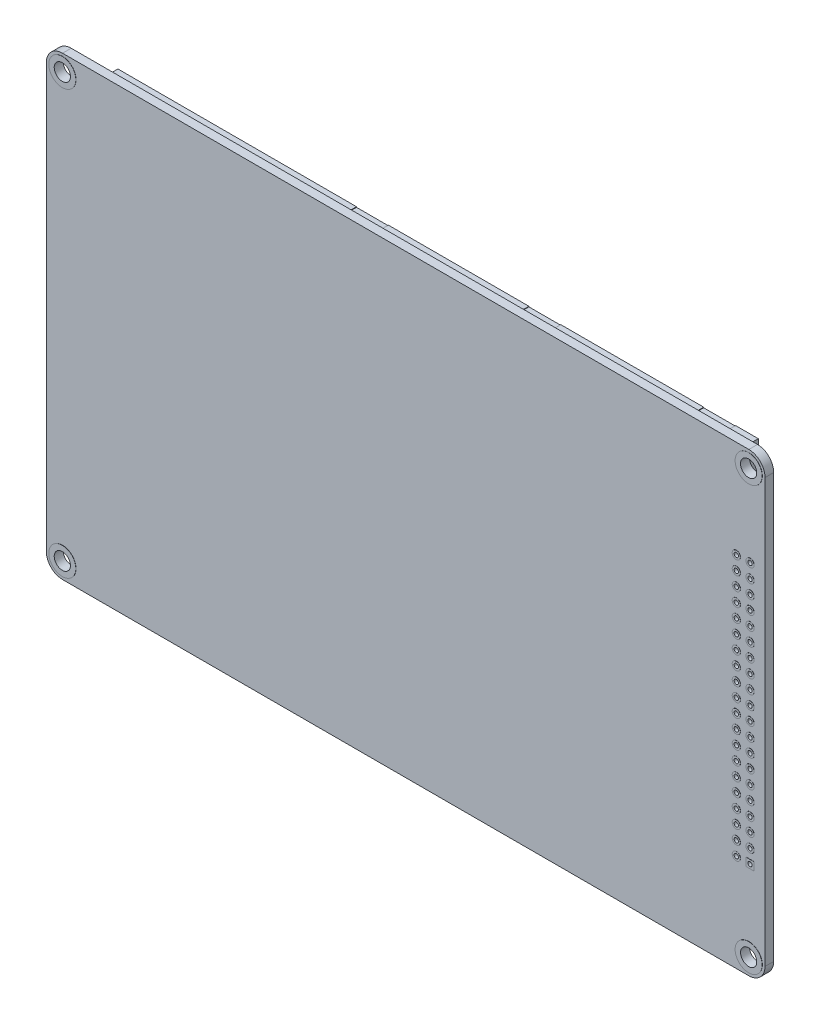
SolidWorks part; units mm, degrees
ref_plane "Plan de face" through (0, 0, 0) normal (0, 0, 1) x (1, 0, 0)
ref_plane "Plan de dessus" through (0, 0, 0) normal (0, 1, 0) x (1, 0, 0)
ref_plane "Plan de droite" through (0, 0, 0) normal (1, 0, 0) x (0, 0, -1)
sketch "Esquisse1" plane through (0, 0, 0) normal (0, 0, 1) x (1, 0, 0)
  line L1 (-66.5, -42.175) -> (66.5, -42.175)
  line L2 (-66.5, -42.175) -> (-66.5, 42.175)
  line L3 (-66.5, 42.175) -> (66.5, 42.175)
  line L4 (66.5, -42.175) -> (66.5, 42.175)
  line L5 (-66.5, -42.175) -> (66.5, 42.175) construction
  line L6 (-66.5, 42.175) -> (66.5, -42.175) construction
  point P0 (0, 0)
  dimension "D1" = 84.35
  dimension "D2" = 133
extrude "Boss.-Extru.1" add sketch "Esquisse1" along normal blind 1.6
sketch "Esquisse2" plane through (0, 0, 1.6) normal (0, 0, 1) x (1, 0, 0)
  line L0 (-66.5, -42.175) -> (66.5, -42.175) construction
  line L1 (-66.5, 42.175) -> (-66.5, -42.175) construction
  line L2 (66.5, -42.175) -> (66.5, 42.175) construction
  line L3 (66.5, 42.175) -> (-66.5, 42.175) construction
  circle A0 centre (-63.5, -39.175) radius 1.5
  circle A1 centre (63.5, -39.175) radius 1.5
  circle A2 centre (-63.5, 39.175) radius 1.5
  circle A3 centre (63.5, 39.175) radius 1.5
  dimension "D1" = 3
  dimension "D6" = 3
  dimension "D7" = 3
  dimension "D2" = 3
  dimension "D3" = 3
  dimension "D4" = 2
  dimension "D5" = 2
extrude "Enlèv. mat.-Extru.1" cut sketch "Esquisse2" against normal blind 10
sketch "Esquisse3" plane through (0, 0, 1.6) normal (0, 0, 1) x (1, 0, 0)
  circle A0 centre (-63.5, -39.175) radius 1.5
  circle A1 centre (-63.5, -39.175) radius 2.5
  circle A2 centre (63.5, -39.175) radius 2.5
  circle A3 centre (63.5, -39.175) radius 1.5
  circle A4 centre (-63.5, 39.175) radius 2.5
  circle A5 centre (-63.5, 39.175) radius 1.5
  circle A6 centre (63.5, 39.175) radius 2.5
  circle A7 centre (63.5, 39.175) radius 1.5
  dimension "D1" = 5
  dimension "D4" = 3
  dimension "D2" = 2
  dimension "D3" = 2
extrude "Boss.-Extru.2" add sketch "Esquisse3" along normal blind 0.035
sketch "Esquisse4" plane through (-66.5, 0, 0) normal (-1, 0, 0) x (0, 0, 1)
  line L0 (1.6, 42.175) -> (0, -42.175) construction
  line L1 (0, -42.175) -> (1.6, -42.175) construction
  line L2 (1.6, -42.175) -> (0, 42.175) construction
  point P4 (0.8, 0)
ref_axis "Axe1" through (-66.5, 0, 0.8) along (-1, 0, 0)
pattern_circular "Répétition circulaire1" count 2 every 180 about axis through (-66.5, 0, 0.8) along (-1, 0, 0) of "Boss.-Extru.2"
sketch "Esquisse5" plane through (0, 0, 1.6) normal (0, 0, 1) x (1, 0, 0)
  line L0 (66.5, -42.175) -> (66.5, 42.175) construction
  line L1 (-66.5, -42.175) -> (66.5, -42.175) construction
  circle A0 centre (63.75, -24.13) radius 0.4
  circle A1 centre (61.21, -24.13) radius 0.4
  circle A2 centre (63.75, -21.59) radius 0.4
  circle A3 centre (61.21, -21.59) radius 0.4
  circle A4 centre (63.75, -19.05) radius 0.4
  circle A5 centre (61.21, -19.05) radius 0.4
  circle A6 centre (63.75, -16.51) radius 0.4
  circle A7 centre (61.21, -16.51) radius 0.4
  circle A8 centre (63.75, -13.97) radius 0.4
  circle A9 centre (61.21, -13.97) radius 0.4
  circle A10 centre (63.75, -11.43) radius 0.4
  circle A11 centre (61.21, -11.43) radius 0.4
  circle A12 centre (63.75, -8.89) radius 0.4
  circle A13 centre (61.21, -8.89) radius 0.4
  circle A14 centre (63.75, -6.35) radius 0.4
  circle A15 centre (61.21, -6.35) radius 0.4
  circle A16 centre (63.75, -3.81) radius 0.4
  circle A17 centre (61.21, -3.81) radius 0.4
  circle A18 centre (63.75, -1.27) radius 0.4
  circle A19 centre (61.21, -1.27) radius 0.4
  circle A20 centre (63.75, 1.27) radius 0.4
  circle A21 centre (61.21, 1.27) radius 0.4
  circle A22 centre (63.75, 3.81) radius 0.4
  circle A23 centre (61.21, 3.81) radius 0.4
  circle A24 centre (63.75, 6.35) radius 0.4
  circle A25 centre (61.21, 6.35) radius 0.4
  circle A26 centre (63.75, 8.89) radius 0.4
  circle A27 centre (61.21, 8.89) radius 0.4
  circle A28 centre (63.75, 11.43) radius 0.4
  circle A29 centre (61.21, 11.43) radius 0.4
  circle A30 centre (63.75, 13.97) radius 0.4
  circle A31 centre (61.21, 13.97) radius 0.4
  circle A32 centre (63.75, 16.51) radius 0.4
  circle A33 centre (61.21, 16.51) radius 0.4
  circle A34 centre (63.75, 19.05) radius 0.4
  circle A35 centre (61.21, 19.05) radius 0.4
  circle A36 centre (63.75, 21.59) radius 0.4
  circle A37 centre (61.21, 21.59) radius 0.4
  circle A38 centre (63.75, 24.13) radius 0.4
  circle A39 centre (61.21, 24.13) radius 0.4
  dimension "D1" = 0.8
  dimension "D6" = 48.26
  dimension "D2" = 2
  dimension "D3" = 20
  dimension "D4" = 2.75
  dimension "D5" = 18.045
extrude "Enlèv. mat.-Extru.2" cut sketch "Esquisse5" against normal through all
sketch "Esquisse6" plane through (0, 0, 1.6) normal (0, 0, 1) x (1, 0, 0)
  line L1 (63, -23.38) -> (64.5, -23.38)
  line L2 (63, -23.38) -> (63, -24.88)
  line L3 (63, -24.88) -> (64.5, -24.88)
  line L4 (64.5, -23.38) -> (64.5, -24.88)
  line L5 (63, -23.38) -> (64.5, -24.88) construction
  line L6 (63, -24.88) -> (64.5, -23.38) construction
  circle A0 centre (63.75, -24.13) radius 0.4
  circle A1 centre (63.75, -24.13) radius 0.4 construction
  circle A2 centre (61.21, -24.13) radius 0.4
  circle A3 centre (61.21, -24.13) radius 0.75
  circle A4 centre (61.21, -21.59) radius 0.75
  circle A5 centre (61.21, -21.59) radius 0.4
  circle A6 centre (61.21, -19.05) radius 0.75
  circle A7 centre (61.21, -19.05) radius 0.4
  circle A8 centre (61.21, -16.51) radius 0.75
  circle A9 centre (61.21, -16.51) radius 0.4
  circle A10 centre (61.21, -13.97) radius 0.75
  circle A11 centre (61.21, -13.97) radius 0.4
  circle A12 centre (61.21, -11.43) radius 0.75
  circle A13 centre (61.21, -11.43) radius 0.4
  circle A14 centre (61.21, -8.89) radius 0.75
  circle A15 centre (61.21, -8.89) radius 0.4
  circle A16 centre (61.21, -6.35) radius 0.75
  circle A17 centre (61.21, -6.35) radius 0.4
  circle A18 centre (61.21, -3.81) radius 0.75
  circle A19 centre (61.21, -3.81) radius 0.4
  circle A20 centre (61.21, -1.27) radius 0.75
  circle A21 centre (61.21, -1.27) radius 0.4
  circle A22 centre (61.21, 1.27) radius 0.75
  circle A23 centre (61.21, 1.27) radius 0.4
  circle A24 centre (61.21, 3.81) radius 0.75
  circle A25 centre (61.21, 3.81) radius 0.4
  circle A26 centre (61.21, 6.35) radius 0.75
  circle A27 centre (61.21, 6.35) radius 0.4
  circle A28 centre (61.21, 8.89) radius 0.75
  circle A29 centre (61.21, 8.89) radius 0.4
  circle A30 centre (61.21, 11.43) radius 0.75
  circle A31 centre (61.21, 11.43) radius 0.4
  circle A32 centre (61.21, 13.97) radius 0.75
  circle A33 centre (61.21, 13.97) radius 0.4
  circle A34 centre (61.21, 16.51) radius 0.75
  circle A35 centre (61.21, 16.51) radius 0.4
  circle A36 centre (61.21, 19.05) radius 0.75
  circle A37 centre (61.21, 19.05) radius 0.4
  circle A38 centre (61.21, 21.59) radius 0.75
  circle A39 centre (61.21, 21.59) radius 0.4
  circle A40 centre (61.21, 24.13) radius 0.75
  circle A41 centre (61.21, 24.13) radius 0.4
  circle A42 centre (63.75, -21.59) radius 0.4
  circle A43 centre (63.75, -21.59) radius 0.75
  circle A44 centre (63.75, -19.05) radius 0.75
  circle A45 centre (63.75, -19.05) radius 0.4
  circle A46 centre (63.75, -16.51) radius 0.75
  circle A47 centre (63.75, -16.51) radius 0.4
  circle A48 centre (63.75, -13.97) radius 0.75
  circle A49 centre (63.75, -13.97) radius 0.4
  circle A50 centre (63.75, -11.43) radius 0.75
  circle A51 centre (63.75, -11.43) radius 0.4
  circle A52 centre (63.75, -8.89) radius 0.75
  circle A53 centre (63.75, -8.89) radius 0.4
  circle A54 centre (63.75, -6.35) radius 0.75
  circle A55 centre (63.75, -6.35) radius 0.4
  circle A56 centre (63.75, -3.81) radius 0.75
  circle A57 centre (63.75, -3.81) radius 0.4
  circle A58 centre (63.75, -1.27) radius 0.75
  circle A59 centre (63.75, -1.27) radius 0.4
  circle A60 centre (63.75, 1.27) radius 0.75
  circle A61 centre (63.75, 1.27) radius 0.4
  circle A62 centre (63.75, 3.81) radius 0.75
  circle A63 centre (63.75, 3.81) radius 0.4
  circle A64 centre (63.75, 6.35) radius 0.75
  circle A65 centre (63.75, 6.35) radius 0.4
  circle A66 centre (63.75, 8.89) radius 0.75
  circle A67 centre (63.75, 8.89) radius 0.4
  circle A68 centre (63.75, 11.43) radius 0.75
  circle A69 centre (63.75, 11.43) radius 0.4
  circle A70 centre (63.75, 13.97) radius 0.75
  circle A71 centre (63.75, 13.97) radius 0.4
  circle A72 centre (63.75, 16.51) radius 0.75
  circle A73 centre (63.75, 16.51) radius 0.4
  circle A74 centre (63.75, 19.05) radius 0.75
  circle A75 centre (63.75, 19.05) radius 0.4
  circle A76 centre (63.75, 21.59) radius 0.75
  circle A77 centre (63.75, 21.59) radius 0.4
  circle A78 centre (63.75, 24.13) radius 0.75
  circle A79 centre (63.75, 24.13) radius 0.4
  dimension "D3" = 1.5
  dimension "D5" = 1.5
  dimension "D1" = 1.5
  dimension "D2" = 1.5
  dimension "D4" = 20
  dimension "D6" = 19
extrude "Boss.-Extru.3" add sketch "Esquisse6" along normal blind 0.035
sketch "Esquisse7" plane through (0, 0, 0) normal (0, 0, -1) x (-1, 0, 0)
  line L1 (-63, 23.38) -> (-64.5, 23.38)
  line L2 (-63, 23.38) -> (-63, 24.88)
  line L3 (-63, 24.88) -> (-64.5, 24.88)
  line L4 (-64.5, 23.38) -> (-64.5, 24.88)
  line L5 (-63, 23.38) -> (-64.5, 24.88) construction
  line L6 (-63, 24.88) -> (-64.5, 23.38) construction
  circle A0 centre (-63.75, -24.13) radius 0.4
  circle A1 centre (-63.75, -24.13) radius 0.4 construction
  circle A2 centre (-61.21, -24.13) radius 0.4
  circle A3 centre (-63.75, -24.13) radius 0.75
  circle A4 centre (-61.21, -24.13) radius 0.75
  circle A5 centre (-63.75, -21.59) radius 0.75
  circle A6 centre (-61.21, -21.59) radius 0.75
  circle A7 centre (-61.21, -21.59) radius 0.4
  circle A8 centre (-61.21, -19.05) radius 0.75
  circle A9 centre (-61.21, -19.05) radius 0.4
  circle A10 centre (-61.21, -16.51) radius 0.75
  circle A11 centre (-61.21, -16.51) radius 0.4
  circle A12 centre (-61.21, -13.97) radius 0.75
  circle A13 centre (-61.21, -13.97) radius 0.4
  circle A14 centre (-61.21, -11.43) radius 0.75
  circle A15 centre (-61.21, -11.43) radius 0.4
  circle A16 centre (-61.21, -8.89) radius 0.75
  circle A17 centre (-61.21, -8.89) radius 0.4
  circle A18 centre (-61.21, -6.35) radius 0.75
  circle A19 centre (-61.21, -6.35) radius 0.4
  circle A20 centre (-61.21, -3.81) radius 0.75
  circle A21 centre (-61.21, -3.81) radius 0.4
  circle A22 centre (-61.21, -1.27) radius 0.75
  circle A23 centre (-61.21, -1.27) radius 0.4
  circle A24 centre (-61.21, 1.27) radius 0.75
  circle A25 centre (-61.21, 1.27) radius 0.4
  circle A26 centre (-61.21, 3.81) radius 0.75
  circle A27 centre (-61.21, 3.81) radius 0.4
  circle A28 centre (-61.21, 6.35) radius 0.75
  circle A29 centre (-61.21, 6.35) radius 0.4
  circle A30 centre (-61.21, 8.89) radius 0.75
  circle A31 centre (-61.21, 8.89) radius 0.4
  circle A32 centre (-61.21, 11.43) radius 0.75
  circle A33 centre (-61.21, 11.43) radius 0.4
  circle A34 centre (-61.21, 13.97) radius 0.75
  circle A35 centre (-61.21, 13.97) radius 0.4
  circle A36 centre (-61.21, 16.51) radius 0.75
  circle A37 centre (-61.21, 16.51) radius 0.4
  circle A38 centre (-61.21, 19.05) radius 0.75
  circle A39 centre (-61.21, 19.05) radius 0.4
  circle A40 centre (-61.21, 21.59) radius 0.75
  circle A41 centre (-61.21, 21.59) radius 0.4
  circle A42 centre (-61.21, 24.13) radius 0.75
  circle A43 centre (-61.21, 24.13) radius 0.4
  circle A44 centre (-63.75, -21.59) radius 0.4
  circle A45 centre (-63.75, -19.05) radius 0.75
  circle A46 centre (-63.75, -19.05) radius 0.4
  circle A47 centre (-63.75, -16.51) radius 0.75
  circle A48 centre (-63.75, -16.51) radius 0.4
  circle A49 centre (-63.75, -13.97) radius 0.75
  circle A50 centre (-63.75, -13.97) radius 0.4
  circle A51 centre (-63.75, -11.43) radius 0.75
  circle A52 centre (-63.75, -11.43) radius 0.4
  circle A53 centre (-63.75, -8.89) radius 0.75
  circle A54 centre (-63.75, -8.89) radius 0.4
  circle A55 centre (-63.75, -6.35) radius 0.75
  circle A56 centre (-63.75, -6.35) radius 0.4
  circle A57 centre (-63.75, -3.81) radius 0.75
  circle A58 centre (-63.75, -3.81) radius 0.4
  circle A59 centre (-63.75, -1.27) radius 0.75
  circle A60 centre (-63.75, -1.27) radius 0.4
  circle A61 centre (-63.75, 1.27) radius 0.75
  circle A62 centre (-63.75, 1.27) radius 0.4
  circle A63 centre (-63.75, 3.81) radius 0.75
  circle A64 centre (-63.75, 3.81) radius 0.4
  circle A65 centre (-63.75, 6.35) radius 0.75
  circle A66 centre (-63.75, 6.35) radius 0.4
  circle A67 centre (-63.75, 8.89) radius 0.75
  circle A68 centre (-63.75, 8.89) radius 0.4
  circle A69 centre (-63.75, 11.43) radius 0.75
  circle A70 centre (-63.75, 11.43) radius 0.4
  circle A71 centre (-63.75, 13.97) radius 0.75
  circle A72 centre (-63.75, 13.97) radius 0.4
  circle A73 centre (-63.75, 16.51) radius 0.75
  circle A74 centre (-63.75, 16.51) radius 0.4
  circle A75 centre (-63.75, 19.05) radius 0.75
  circle A76 centre (-63.75, 19.05) radius 0.4
  circle A77 centre (-63.75, 21.59) radius 0.75
  circle A78 centre (-63.75, 21.59) radius 0.4
  circle A79 centre (-63.75, 24.13) radius 0.4
  circle A117 centre (-63.75, 24.13) radius 0.4 construction
  dimension "D3" = 1.5
  dimension "D4" = 1.5
  dimension "D1" = 1.5
  dimension "D2" = 19
  dimension "D7" = 1.5
  dimension "D5" = 20
extrude "Boss.-Extru.4" add sketch "Esquisse7" along normal blind 0.035
sketch "Esquisse8" plane through (0, 0, 0) normal (0, 0, -1) x (-1, 0, 0)
  line L0 (66.5, -42.175) -> (-66.5, -42.175) construction
  line L1 (59.25, -38.775) -> (-59.25, -38.775)
  line L2 (59.25, -38.775) -> (59.25, 38.775)
  line L3 (59.25, 38.775) -> (-59.25, 38.775)
  line L4 (-59.25, -38.775) -> (-59.25, 38.775)
  line L5 (59.25, -38.775) -> (-59.25, 38.775) construction
  line L6 (59.25, 38.775) -> (-59.25, -38.775) construction
  line L8 (-66.5, -42.175) -> (-66.5, 42.175) construction
  dimension "D1" = 77.55
  dimension "D2" = 118.5
  dimension "D3" = 7.25
  dimension "D4" = 3.4
extrude "Boss.-Extru.5" add sketch "Esquisse8" along normal blind 4.4
sketch "Esquisse9" plane through (0, 0, -4.4) normal (0, 0, -1) x (-1, 0, 0)
  line L0 (59.25, -38.775) -> (59.25, 38.775) construction
  line L1 (58.95, -38.475) -> (-58.95, -38.475)
  line L2 (58.95, -38.475) -> (58.95, 38.475)
  line L3 (58.95, 38.475) -> (-58.95, 38.475)
  line L4 (-58.95, -38.475) -> (-58.95, 38.475)
  line L5 (58.95, -38.475) -> (-58.95, 38.475) construction
  line L6 (58.95, 38.475) -> (-58.95, -38.475) construction
  line L7 (59.25, 38.775) -> (-59.25, 38.775) construction
  line L9 (-59.25, 38.775) -> (-59.25, -38.775) construction
  line L10 (-59.25, -38.775) -> (59.25, -38.775) construction
  point P0 (0, 0)
  point P6 (59.25, 0)
  dimension "D1" = 0.3
  dimension "D2" = 0.3
  dimension "D3" = 0.3
  dimension "D4" = 0.3
extrude "Enlèv. mat.-Extru.3" cut sketch "Esquisse9" against normal blind 3
sketch "Esquisse11" plane through (0, 38.775, 0) normal (0, 1, 0) x (1, 0, 0)
  line L0 (57.85, 0) -> (57.85, 2.4)
  line L1 (-59.25, 0) -> (59.25, 0) construction
  line L2 (59.25, 4.4) -> (59.25, 0) construction
  line L3 (57.85, 2.4) -> (55.05, 2.4)
  line L4 (55.05, 2.4) -> (55.05, 4.4)
  line L5 (-59.25, 4.4) -> (59.25, 4.4) construction
  line L6 (55.05, 4.4) -> (49.15, 4.4)
  line L7 (49.15, 4.4) -> (49.15, 2.4)
  line L8 (49.15, 2.4) -> (22.7, 2.4)
  line L9 (53.85, 0) -> (53.85, 1.3)
  line L10 (53.65, 1.5) -> (50.95, 1.5)
  line L11 (50.75, 1.3) -> (50.75, 0)
  line L12 (53.85, 0) -> (57.85, 0)
  line L13 (22.7, 2.4) -> (22.7, 4.4)
  line L14 (22.7, 4.4) -> (16.8, 4.4)
  line L15 (16.8, 4.4) -> (16.8, 2.4)
  line L16 (16.8, 2.4) -> (-9.2, 2.4)
  line L17 (-9.2, 2.4) -> (-9.2, 4.4)
  line L18 (-9.2, 4.4) -> (-15.1, 4.4)
  line L19 (-15.1, 4.4) -> (-15.1, 2.4)
  line L20 (-15.1, 2.4) -> (-57.85, 2.4)
  line L21 (-59.25, 4.4) -> (-59.25, 0) construction
  line L22 (-57.85, 2.4) -> (-57.85, 0)
  line L23 (18.4, 1.5) -> (21.1, 1.5)
  line L24 (21.3, 1.3) -> (21.3, 0)
  line L25 (18.2, 1.3) -> (18.2, 0)
  line L26 (21.3, 0) -> (50.75, 0)
  line L27 (-13.7, 0) -> (-13.7, 1.3)
  line L28 (-13.5, 1.5) -> (-10.8, 1.5)
  line L29 (-10.6, 1.3) -> (-10.6, 0)
  line L30 (-10.6, 0) -> (18.2, 0)
  line L31 (-57.85, 0) -> (-13.7, 0)
  line L32 (0, 0) -> (0, 4.4) construction
  arc A0 (-10.8, 1.5) -> (-10.6, 1.3) centre (-10.8, 1.3) cw
  arc A1 (-13.7, 1.3) -> (-13.5, 1.5) centre (-13.5, 1.3) cw
  arc A2 (53.85, 1.3) -> (53.65, 1.5) centre (53.65, 1.3) ccw
  arc A3 (50.95, 1.5) -> (50.75, 1.3) centre (50.95, 1.3) ccw
  arc A4 (21.1, 1.5) -> (21.3, 1.3) centre (21.1, 1.3) cw
  arc A5 (18.4, 1.5) -> (18.2, 1.3) centre (18.4, 1.3) ccw
  point P41 (-10.6, 1.5)
  point P44 (-13.7, 1.5)
  point P47 (53.85, 1.5)
  point P50 (50.75, 1.5)
  point P53 (21.3, 1.5)
  point P56 (18.2, 1.5)
  dimension "D23" = 0.2
  dimension "D1" = 1.4
  dimension "D2" = 4.2
  dimension "D3" = 5.9
  dimension "D4" = 2
  dimension "D5" = 2
  dimension "D6" = 26.45
  dimension "D7" = 3.1
  dimension "D8" = 4
  dimension "D9" = 1.5
  dimension "D10" = 2
  dimension "D11" = 5.9
  dimension "D12" = 26
  dimension "D13" = 2
  dimension "D14" = 5.9
  dimension "D15" = 1.4
  dimension "D16" = 1.4
  dimension "D17" = 1.5
  dimension "D18" = 3.1
  dimension "D19" = 3.1
  dimension "D20" = 1.4
  dimension "D21" = 1.5
  dimension "D22" = 49.15
extrude "Enlèv. mat.-Extru.7" cut sketch "Esquisse11" against normal blind 0.1
sketch "Esquisse13" plane through (-59.25, 0, 0) normal (-1, 0, 0) x (0, 0, 1)
  line L0 (-4.4, -2.95) -> (-4.4, 2.95)
  line L1 (-4.4, 2.95) -> (-2.4, 2.95)
  line L2 (0, 0) -> (-4.4, 0) construction
  line L3 (0, -38.775) -> (0, 38.775) construction
  line L4 (-4.4, -38.775) -> (-4.4, 38.775) construction
  line L5 (-4.4, -2.95) -> (-2.4, -2.95)
  line L6 (0, 37.375) -> (-2.4, 37.375)
  line L7 (-4.4, 38.775) -> (0, 38.775) construction
  line L8 (-2.4, 37.375) -> (-2.4, 34.575)
  line L9 (-2.4, 34.575) -> (-4.4, 34.575)
  line L10 (-4.4, 34.575) -> (-4.4, 28.675)
  line L11 (-4.4, 28.675) -> (-2.4, 28.675)
  line L12 (-2.4, 28.675) -> (-2.4, 2.95)
  line L13 (0, 30.075) -> (-1.3, 30.075)
  line L14 (-1.5, 30.275) -> (-1.5, 32.975)
  line L15 (-1.3, 33.175) -> (0, 33.175)
  line L16 (0, -37.375) -> (-2.4, -37.375)
  line L17 (-2.4, -37.375) -> (-2.4, -34.575)
  line L18 (-2.4, -34.575) -> (-4.4, -34.575)
  line L19 (-4.4, -34.575) -> (-4.4, -28.675)
  line L20 (-4.4, -28.675) -> (-2.4, -28.675)
  line L21 (-2.4, -28.675) -> (-2.4, -2.95)
  line L22 (-4.4, -38.775) -> (0, -38.775) construction
  line L23 (0, -1.55) -> (-1.3, -1.55)
  line L24 (-1.5, -1.35) -> (-1.5, 1.35)
  line L25 (-1.3, 1.55) -> (0, 1.55)
  line L26 (0, -33.175) -> (-1.3, -33.175)
  line L27 (-1.5, -32.975) -> (-1.5, -30.275)
  line L28 (-1.3, -30.075) -> (0, -30.075)
  line L29 (0, -37.375) -> (0, -33.175)
  line L30 (0, -30.075) -> (0, -1.55)
  line L31 (0, 1.55) -> (0, 30.075)
  line L32 (0, 33.175) -> (0, 37.375)
  arc A0 (-1.3, -33.175) -> (-1.5, -32.975) centre (-1.3, -32.975) cw
  arc A1 (-1.5, -30.275) -> (-1.3, -30.075) centre (-1.3, -30.275) cw
  arc A2 (-1.3, -1.55) -> (-1.5, -1.35) centre (-1.3, -1.35) cw
  arc A3 (-1.5, 1.35) -> (-1.3, 1.55) centre (-1.3, 1.35) cw
  arc A4 (-1.3, 30.075) -> (-1.5, 30.275) centre (-1.3, 30.275) cw
  arc A5 (-1.5, 32.975) -> (-1.3, 33.175) centre (-1.3, 32.975) cw
  point P44 (-1.5, -33.175)
  point P47 (-1.5, -30.075)
  point P50 (-1.5, -1.55)
  point P53 (-1.5, 1.55)
  point P56 (-1.5, 30.075)
  point P59 (-1.5, 33.175)
  dimension "D20" = 0.2
  dimension "D1" = 5.9
  dimension "D2" = 2.95
  dimension "D3" = 2
  dimension "D4" = 2
  dimension "D5" = 1.4
  dimension "D6" = 2.4
  dimension "D7" = 4.2
  dimension "D8" = 5.9
  dimension "D9" = 2
  dimension "D10" = 1.4
  dimension "D11" = 3.1
  dimension "D12" = 1.5
  dimension "D13" = 4.2
  dimension "D14" = 1.4
  dimension "D15" = 5.9
  dimension "D16" = 3.1
  dimension "D17" = 1.4
  dimension "D18" = 3.1
  dimension "D19" = 1.4
extrude "Enlèv. mat.-Extru.8" cut sketch "Esquisse13" against normal blind 0.1
sketch "Esquisse14" plane through (59.25, 0, 0) normal (1, 0, 0) x (0, 0, -1)
  line L0 (4.4, 38.775) -> (4.4, -38.775) construction
  line L1 (4.4, -34.075) -> (1, -34.075)
  line L2 (4.4, -34.075) -> (4.4, 36.475)
  line L3 (4.4, 36.475) -> (1, 36.475)
  line L4 (1, -34.075) -> (1, 36.475)
  line L5 (4.4, -38.775) -> (0, -38.775) construction
  line L6 (4.4, 38.775) -> (0, 38.775) construction
  line L7 (0, 38.775) -> (0, -38.775) construction
  dimension "D1" = 4.7
  dimension "D2" = 2.3
  dimension "D3" = 1
extrude "Enlèv. mat.-Extru.9" cut sketch "Esquisse14" against normal blind 0.3
sketch "Esquisse15" plane through (0, -42.175, 0) normal (0, -1, 0) x (1, 0, 0)
  point P4 (0, 0.8)
ref_axis "Axe2" through (0, -42.175, 0.8) along (0, -1, 0)
sketch "Esquisse16" plane through (0, 0, -1.4) normal (0, 0, -1) x (-1, 0, 0)
  line L0 (56.95, -36.475) -> (56.95, 36.475)
  line L1 (58.95, -38.475) -> (58.95, 38.475) construction
  line L2 (-58.95, -38.475) -> (58.95, -38.475) construction
  line L3 (58.95, 38.475) -> (-58.95, 38.475) construction
  line L4 (56.95, 36.475) -> (-54.95, 36.475)
  line L5 (-58.95, 38.475) -> (-58.95, 36.475) construction
  line L6 (-54.95, 36.475) -> (-54.95, -36.475)
  line L7 (-54.95, -36.475) -> (56.95, -36.475)
  dimension "D1" = 2
  dimension "D2" = 2
  dimension "D3" = 2
  dimension "D4" = 4
  dimension "D5" = 2
extrude "Boss.-Extru.6" add sketch "Esquisse16" along normal blind 3
sketch "Esquisse19" plane through (0, 0, -1.4) normal (0, 0, -1) x (-1, 0, 0)
  line L0 (58.95, 38.475) -> (-58.95, 38.475) construction
  line L1 (57, -36.525) -> (-55, -36.525)
  line L2 (57, -36.525) -> (57, 36.525)
  line L3 (57, 36.525) -> (-55, 36.525)
  line L4 (-55, -36.525) -> (-55, 36.525)
  line L5 (-58.95, 38.425) -> (58.9, 38.425)
  line L6 (-58.95, 38.425) -> (-58.95, -38.425)
  line L7 (-58.95, -38.425) -> (58.9, -38.425)
  line L8 (58.9, 38.425) -> (58.9, -38.425)
  line L9 (-54.95, 36.475) -> (-54.95, -36.475) construction
  line L10 (56.95, 36.475) -> (-54.95, 36.475) construction
  line L11 (-54.95, -36.475) -> (56.95, -36.475) construction
  line L12 (-58.95, -38.475) -> (58.95, -38.475) construction
  line L13 (58.95, -38.475) -> (58.95, 38.475) construction
  line L14 (56.95, -36.475) -> (56.95, 36.475) construction
  line L15 (-58.95, -34.075) -> (-58.95, -38.475) construction
  dimension "D1" = 0.05
  dimension "D2" = 0.05
  dimension "D3" = 0.05
  dimension "D4" = 0.05
  dimension "D5" = 0.05
  dimension "D6" = 0.05
  dimension "D7" = 0.05
extrude "Boss.-Extru.9" add sketch "Esquisse19" along normal blind 3
sketch "Esquisse20" plane through (0, 0, 0) normal (0, 0, -1) x (-1, 0, 0)
  line L1 (-60.21, -25.13) -> (-64.75, -25.13)
  line L2 (-60.21, -25.13) -> (-60.21, 25.13)
  line L3 (-60.21, 25.13) -> (-64.75, 25.13)
  line L4 (-64.75, -25.13) -> (-64.75, 25.13)
  line L6 (-60.01, 25.33) -> (-64.95, 25.33)
  line L7 (-60.01, 25.33) -> (-60.01, -25.33)
  line L8 (-60.01, -25.33) -> (-64.95, -25.33)
  line L9 (-64.95, 25.33) -> (-64.95, -25.33)
  circle A3 centre (-61.21, -24.13) radius 0.75 construction
  circle A5 centre (-63.75, 24.13) radius 0.4 construction
  dimension "D1" = 1
  dimension "D2" = 1
  dimension "D3" = 1
  dimension "D4" = 1
  dimension "D5" = 0.2
  dimension "D6" = 0.2
  dimension "D7" = 0.2
  dimension "D8" = 0.2
extrude "Boss.-Extru.10" add sketch "Esquisse20" along normal blind 0.01
sketch "Esquisse21" plane through (0, 0, 0) normal (0, 0, -1) x (-1, 0, 0)
  line L0 (-59.25, 38.775) -> (-59.25, -38.775) construction
  line L1 (59.45, 38.975) -> (-59.45, 38.975)
  line L2 (59.45, 38.975) -> (59.45, -38.975)
  line L3 (59.45, -38.975) -> (-59.45, -38.975)
  line L4 (-59.45, 38.975) -> (-59.45, -38.975)
  line L5 (-59.25, -38.775) -> (59.25, -38.775) construction
  line L7 (59.25, 37.375) -> (59.25, 38.775) construction
  line L8 (59.25, 38.775) -> (57.85, 38.775) construction
  line L10 (59.65, 39.175) -> (-59.65, 39.175)
  line L11 (59.65, 39.175) -> (59.65, -39.175)
  line L12 (59.65, -39.175) -> (-59.65, -39.175)
  line L13 (-59.65, 39.175) -> (-59.65, -39.175)
  dimension "D1" = 0.2
  dimension "D2" = 0.2
  dimension "D3" = 0.2
  dimension "D4" = 0.2
  dimension "D5" = 0.2
  dimension "D6" = 0.2
  dimension "D7" = 0.2
  dimension "D8" = 0.2
extrude "Boss.-Extru.11" add sketch "Esquisse21" along normal blind 0.01
sketch "Esquisse23" plane through (0, 38.675, 0) normal (0, 1, 0) x (1, 0, 0)
  line L0 (49.15, 2.4) -> (22.7, 2.4) construction
  line L1 (-57.85, 0) -> (27.2, 0)
  line L2 (-57.85, 0) -> (-57.85, 2.2)
  line L3 (-57.65, 2.4) -> (27, 2.4)
  line L4 (27.2, 0) -> (27.2, 2.2)
  line L5 (22.7, 2.4) -> (22.7, 4.4) construction
  arc A0 (-57.85, 2.2) -> (-57.65, 2.4) centre (-57.65, 2.2) cw
  arc A1 (27, 2.4) -> (27.2, 2.2) centre (27, 2.2) cw
  point P13 (27.2, 2.4)
  dimension "D2" = 0.2
  dimension "D1" = 4.5
extrude "Boss.-Extru.13" add sketch "Esquisse23" along normal blind 0.08
pattern_linear "Répétition linéaire2" count 2 spacing 57.38 along (0, -1, 0) of "Boss.-Extru.13"
sketch "Esquisse24" plane through (0, 0, -1.4) normal (0, 0, -1) x (-1, 0, 0)
  line L0 (-58.95, -38.475) -> (58.95, -38.475) construction
  line L1 (-59, 38.425) -> (-58.9, 38.425)
  line L2 (-59, 38.425) -> (-59, -38.425)
  line L3 (-59, -38.425) -> (-58.9, -38.425)
  line L4 (-58.9, 38.425) -> (-58.9, -38.425)
  line L5 (-58.95, -38.425) -> (-58.95, -38.475) construction
  line L6 (-58.95, 38.425) -> (-58.95, -38.425) construction
  line L7 (58.95, 38.475) -> (-58.95, 38.475) construction
  dimension "D1" = 0.05
  dimension "D2" = 0.05
  dimension "D3" = 0.05
  dimension "D4" = 0.05
extrude "Boss.-Extru.14" add sketch "Esquisse24" along normal blind 3
fillet "Filete2" radius 3 4 edges at (66.5, 42.175, 0.8) (-66.5, 42.175, 0.8) (-66.5, -42.175, 0.8) (66.5, -42.175, 0.8)
